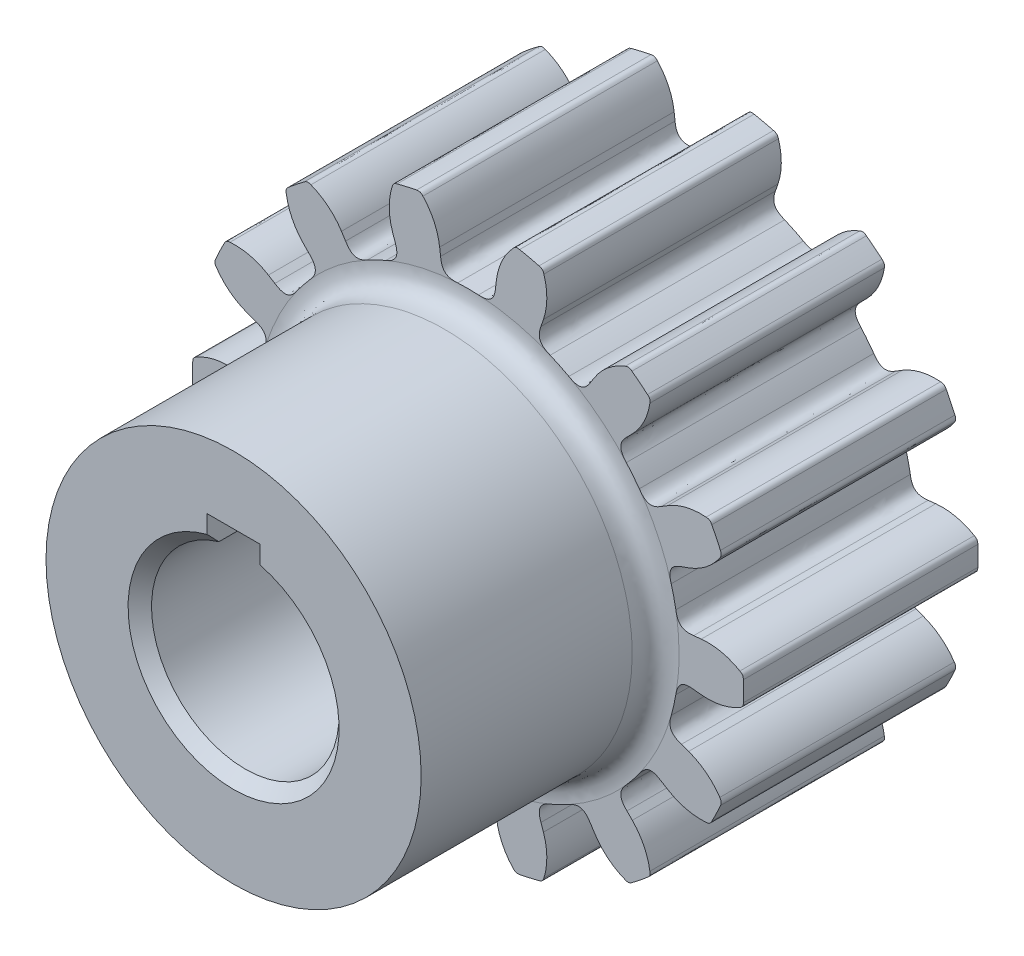
SolidWorks part; units mm, degrees
ref_plane "Front Plane" through (0, 0, 0) normal (0, 0, 1) x (1, 0, 0)
ref_plane "Top Plane" through (0, 0, 0) normal (0, 1, 0) x (1, 0, 0)
ref_plane "Right Plane" through (0, 0, 0) normal (1, 0, 0) x (0, 0, -1)
sketch "Sketch1" plane through (0, 0, 0) normal (0, 0, 1) x (1, 0, 0)
  line L0 (0, 0) -> (22.9641, 0) construction
  line L1 (0, 0) -> (23.1523, 1.1526) construction
  line L2 (0, 0) -> (21.9247, 5.8747) construction
  line L3 (0, 0) -> (22.8611, 2.3625) construction
  line L4 (9.947, 1.0279) -> (8.9523, 0.9251)
  line L5 (8.6933, 2.3294) -> (0, 0)
  line L6 (8.6933, -2.3294) -> (0, 0)
  line L7 (9.947, -1.0279) -> (8.9523, -0.9251)
  circle A0 centre (0, 0) radius 11.75
  circle A1 centre (0, 0) radius 10
  circle A2 centre (0, 0) radius 9
  arc A3 (9.947, 1.0279) -> (11.7355, 0.5842) centre (10.2262, -1.6732) cw
  arc A4 (9.947, -1.0279) -> (11.7355, -0.5842) centre (10.2262, 1.6732) ccw
  circle A5 centre (0, 0) radius 4
  dimension "D1" = 23.5
  dimension "D2" = 20
  dimension "D3" = 18
  dimension "D7" = 8
  dimension "D4" = 15
  dimension "D5" = 5.9
  dimension "D6" = 2.85
extrude "Boss-Extrude1" add sketch "Sketch1" along normal blind 10 contours A5 L6 A2 L5 | A2 L7 A1 L4 | A1 A4 A0 A3 region at (9.492, 0, 0) region at (10.7926, 0, 0) region at (6.7429, 0, 0)
fillet "Fillet1" radius 0.7 2 edges at (8.9523, -0.9251, 5) (8.9523, 0.9251, 5) curvature continuous yes
fillet "Fillet2" radius 0.3 2 edges at (11.7355, -0.5842, 5) (11.7355, 0.5842, 5) curvature continuous yes
ref_axis "Axis1" through (0, 0, 10.555) along (0, 0, -1)
pattern_circular "CirPattern1" count 14 over 360 about axis through (0, 0, 10.555) along (0, 0, -1) of "Boss-Extrude1", "Fillet1", "Fillet2"
sketch "Sketch2" plane through (0, 0, 10) normal (0, 0, 1) x (1, 0, 0)
  circle A0 centre (0, 0) radius 8
  circle A1 centre (0, 0) radius 4 construction
  circle A2 centre (0, 0) radius 4
  dimension "D1" = 16
extrude "Boss-Extrude2" add sketch "Sketch2" along normal blind 10
sketch "Sketch3" plane through (0, 0, 20) normal (0, 0, 1) x (1, 0, 0)
  line L1 (-1.125, 5.125) -> (1.125, 5.125)
  line L2 (-1.125, 5.125) -> (-1.125, 2.875)
  line L3 (-1.125, 2.875) -> (1.125, 2.875)
  line L4 (1.125, 5.125) -> (1.125, 2.875)
  line L5 (-1.125, 5.125) -> (1.125, 2.875) construction
  line L6 (-1.125, 2.875) -> (1.125, 5.125) construction
  circle A0 centre (0, 0) radius 4 construction
  point P0 (0, 4)
  point P7 (0, 0)
  dimension "D1" = 2.25
extrude "Cut-Extrude1" cut sketch "Sketch3" against normal through all
chamfer "Chamfer1" distance 0.5 angle 45 2 edges at (0, -4, 0) (0, -4, 20)
fillet "Fillet3" radius 1 1 edges at (8, 0, 10) curvature continuous yes
